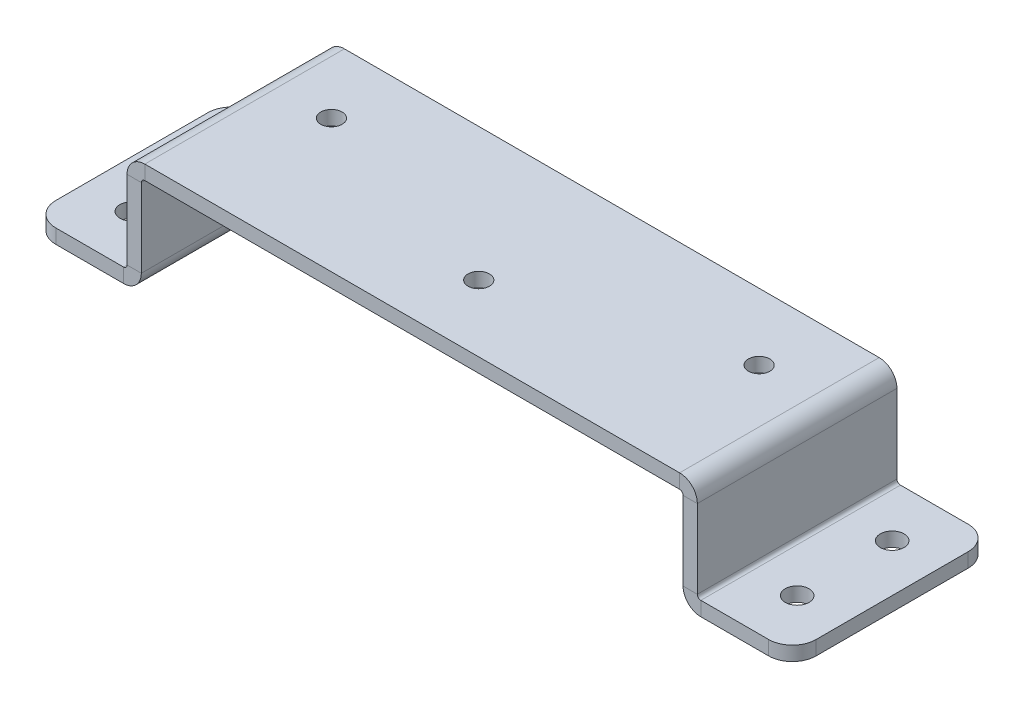
SolidWorks part; units mm, degrees
note: The reader was unsure of these and kept them because the rebuilt part matched: flange length of "모서리 플랜지1", "모서리 플랜지2".
ref_plane "정면" through (0, 0, 0) normal (0, 0, 1) x (1, 0, 0)
ref_plane "윗면" through (0, 0, 0) normal (0, 1, 0) x (1, 0, 0)
ref_plane "우측면" through (0, 0, 0) normal (1, 0, 0) x (0, 0, -1)
sketch "스케치1" plane through (0, 0, 0) normal (0, 1, 0) x (1, 0, 0)
  line L1 (60, -21) -> (-60, -21)
  line L2 (60, -21) -> (60, 21)
  line L3 (60, 21) -> (-60, 21)
  line L4 (-60, -21) -> (-60, 21)
  line L5 (60, -21) -> (-60, 21) construction
  line L6 (60, 21) -> (-60, -21) construction
  point P0 (0, 0)
  dimension "D1" = 120
  dimension "D2" = 42
base flange "베이스-플랜지1" sketch "스케치1" thickness 3 reverse thickness direction no parameters "D1"=0.7366
edge flange "모서리 플랜지1" sketch "스케치10" flange profiles "스케치10", "스케치11" flange angle 90 flange length 24 flange position material inside bend radius 0.7366 thickness 3 relief rectangular parameters "D6"=10, "D8"=1
sketch "스케치10" plane through (-60, -3, 0) normal (-1, 0, 0) x (0, 0, -1)
  line L0 (21, 0) -> (-21, 0) construction
  line L1 (21, 0) -> (-21, 0)
  line L2 (-21, 0) -> (-21, 21)
  line L3 (-21, 21) -> (21, 21)
  line L4 (21, 21) -> (21, 0)
sketch "스케치11" plane through (60, -3, 0) normal (1, 0, 0) x (0, 0, 1)
  line L0 (21, 0) -> (-21, 0) construction
  line L1 (21, 0) -> (-21, 0)
  line L2 (-21, 0) -> (-21, 21)
  line L3 (-21, 21) -> (21, 21)
  line L4 (21, 21) -> (21, 0)
bend "모서리 굽힘1" bend radius 0.7366 bend angle 90 parameters "D5"=1
bend "모서리 굽힘2" bend radius 0.7366 bend angle 90 parameters "D5"=2
edge flange "모서리 플랜지2" sketch "스케치16" flange profiles "스케치16", "스케치17" flange angle 90 flange length 20 flange position material inside bend radius 0.7366 thickness 3 relief rectangular parameters "D6"=10, "D8"=1
sketch "스케치16" plane through (-60, -24, 0) normal (0, -1, 0) x (0, 0, 1)
  line L2 (-21, 0) -> (-21, 20)
  line L3 (-21, 20) -> (21, 20)
  line L4 (21, 20) -> (21, 0)
  line L7 (-21, 0) -> (21, 0) construction
  line L8 (-21, 0) -> (21, 0)
sketch "스케치17" plane through (60, -24, 0) normal (0, -1, 0) x (0, 0, -1)
  line L0 (-21, 0) -> (21, 0) construction
  line L1 (-21, 0) -> (21, 0)
  line L2 (-21, 0) -> (-21, 20)
  line L3 (-21, 20) -> (21, 20)
  line L4 (21, 20) -> (21, 0)
bend "모서리 굽힘3" bend radius 0.7366 bend angle 90 parameters "D5"=3
bend "모서리 굽힘4" bend radius 0.7366 bend angle 90 parameters "D5"=4
fillet "필렛1" radius 5 4 edges at (-80, -22.5, 21) (-80, -22.5, -21) (80, -22.5, -21) (80, -22.5, 21)
sketch "스케치18" plane through (0, -24, 0) normal (0, -1, 0) x (1, 0, 0)
  line L0 (-70, -10) -> (-70, 10) construction
  line L1 (70, 10) -> (70, -10) construction
  line L2 (80, -16) -> (80, 16) construction
  line L3 (-80, 16) -> (-80, -16) construction
  point P0 (70, -10)
  point P1 (70, 10)
  point P2 (-70, 10)
  point P3 (-70, -10)
  point P11 (70, 0)
  dimension "D1" = 20
  dimension "D2" = 10
  dimension "D3" = 10
hole_wizard "M6 탭을 위한 탭 드릴1" positions "스케치19" profile "스케치20" hole size "M6" standard "ISO" end condition up to next
sketch "스케치19" plane through (0, -24, 0) normal (0, -1, 0) x (-1, 0, 0)
  point P0 (-70, 10)
  point P3 (-70, -10)
  point P6 (70, 10)
  point P9 (70, -10)
sketch "스케치20" plane through (70, -24, -10) normal (1, 0, 0) x (0, 0, -1)
  line L0 (0, 0) -> (0, 3)
  line L1 (0, 3) -> (2.5, 3)
  line L2 (2.5, 3) -> (2.5, 0)
  line L5 (2.5, 0) -> (0, 0)
  line L11 (0, -6.35) -> (0, 107.95) construction
  dimension "관통 구멍 지름" = 5
  dimension "관통 구멍 깊이" = 3
sketch "스케치21" plane through (0, 0, 0) normal (0, 1, 0) x (1, 0, 0)
  line L0 (-45, 7) -> (45, 7) construction
  point P0 (-45, 7)
  point P1 (0, -7)
  point P2 (45, 7)
  point P7 (0, 7)
  dimension "D1" = 14
  dimension "D2" = 7
  dimension "D3" = 90
hole_wizard "M4 여유 구멍1" positions "스케치22" profile "스케치23" hole size "M4" standard "ISO" end condition up to next
sketch "스케치22" plane through (0, 0, 0) normal (0, 1, 0) x (1, 0, 0)
  point P0 (-45, 7)
  point P3 (0, -7)
  point P6 (45, 7)
sketch "스케치23" plane through (-45, 0, -7) normal (1, 0, 0) x (0, 0, 1)
  line L0 (0, 0) -> (0, 3)
  line L1 (0, 3) -> (2.25, 3)
  line L2 (2.25, 3) -> (2.25, 0)
  line L5 (2.25, 0) -> (0, 0)
  line L11 (0, -6.35) -> (0, 107.95) construction
  dimension "관통 구멍 지름" = 4.5
  dimension "관통 구멍 깊이" = 3
sketch "굽힘 선1" [suppressed] plane through (0, 0, 0) normal (0, 1, 0) x (1, 0, 0)
sketch "경계 상자1" [suppressed] plane through (0, 0, 0) normal (0, 1, 0) x (1, 0, 0)
sheet metal parameters "판금2" thickness 3 parameters "D1"=0.7366
flat pattern "전개도2" [suppressed]
sketch "굽힘 선2" plane through (0, 0, 0) normal (0, 1, 0) x (1, 0, 0)
sketch3d "경계 상자2" [suppressed]
  line L0 (-75, -15, 0) -> (75, -15, 0) construction
  line L1 (-75, 15, 0) -> (75, 15, 0) construction
  line L2 (-75, -15, 0) -> (-75, 15, 0) construction
  line L3 (75, -15, 0) -> (75, 15, 0) construction
sheet metal parameters "판금3" thickness 3 parameters "D1"=0.7366
flat pattern "전개도2"
sketch "굽힘 선2" plane through (0, 0, 0) normal (0, 1, 0) x (1, 0, 0)
  line L0 (73.02, -15) -> (73.02, 15) construction
  line L1 (-73.02, 15) -> (-73.02, -15) construction
  line L2 (73.02, -15) -> (73.02, 15) construction
  line L3 (-73.02, 15) -> (-73.02, -15) construction
sketch3d "경계 상자2" [suppressed]
  line L0 (98.04, -15, 0) -> (-98.04, -15, 0) construction
  line L1 (98.04, 15, 0) -> (-98.04, 15, 0) construction
  line L2 (98.04, -15, 0) -> (98.04, 15, 0) construction
  line L3 (-98.04, -15, 0) -> (-98.04, 15, 0) construction
bend of the flat pattern "전개도-<모서리 굽힘1>1"
bend of the flat pattern "전개도-<모서리 굽힘2>1"
sheet metal parameters "판금4" thickness 3 parameters "D1"=0.7366
flat pattern "전개도2"
sketch "굽힘 선2" plane through (0, 0, 0) normal (0, 1, 0) x (1, 0, 0)
  line L0 (73.02, -15) -> (73.02, 15) construction
  line L1 (-73.02, 15) -> (-73.02, -15) construction
  line L2 (73.02, -15) -> (73.02, 15) construction
  line L3 (-73.02, 15) -> (-73.02, -15) construction
  line L4 (96.0601, -15) -> (96.0601, 15) construction
  line L5 (-96.0601, 15) -> (-96.0601, -15) construction
  line L6 (96.0601, -15) -> (96.0601, 15) construction
  line L7 (-96.0601, 15) -> (-96.0601, -15) construction
sketch3d "경계 상자2" [suppressed]
  line L0 (-117.0801, -15, 0) -> (117.0801, -15, 0) construction
  line L1 (-117.0801, 15, 0) -> (117.0801, 15, 0) construction
  line L2 (-117.0801, -15, 0) -> (-117.0801, 15, 0) construction
  line L3 (117.0801, -15, 0) -> (117.0801, 15, 0) construction
bend of the flat pattern "전개도-<모서리 굽힘1>1"
bend of the flat pattern "전개도-<모서리 굽힘2>1"
bend of the flat pattern "전개도-<모서리 굽힘3>1"
bend of the flat pattern "전개도-<모서리 굽힘4>1"
sheet metal parameters "판금5" thickness 3 parameters "D1"=0.7366
flat pattern "전개도2" [suppressed]
sketch "굽힘 선2" plane through (0, 0, 0) normal (0, 1, 0) x (1, 0, 0)
  line L0 (68.02, -21) -> (68.02, 21) construction
  line L1 (-68.02, 21) -> (-68.02, -21) construction
  line L2 (68.02, -21) -> (68.02, 21) construction
  line L3 (-68.02, 21) -> (-68.02, -21) construction
  line L4 (88.0601, -21) -> (88.0601, 21) construction
  line L5 (-88.0601, 21) -> (-88.0601, -21) construction
  line L6 (88.0601, -21) -> (88.0601, 21) construction
  line L7 (-88.0601, 21) -> (-88.0601, -21) construction
sketch3d "경계 상자2" [suppressed]
  line L0 (-109.0801, -21, 0) -> (109.0801, -21, 0) construction
  line L1 (-109.0801, 21, 0) -> (109.0801, 21, 0) construction
  line L2 (-109.0801, -21, 0) -> (-109.0801, 21, 0) construction
  line L3 (109.0801, -21, 0) -> (109.0801, 21, 0) construction
bend of the flat pattern "전개도-<모서리 굽힘1>1"
bend of the flat pattern "전개도-<모서리 굽힘2>1"
bend of the flat pattern "전개도-<모서리 굽힘3>1"
bend of the flat pattern "전개도-<모서리 굽힘4>1"
sketch "스케치18-1" plane through (-19.0801, -3, 0) normal (0, -1, 0) x (1, 0, 0)
  line L0 (-80, -10) -> (-80, 10) construction
  line L1 (80, 10) -> (80, -10) construction
  line L2 (128.1602, -16) -> (128.1602, 16)
  line L3 (-90, 16) -> (-90, -16)
  point P0 (80, -10)
  point P1 (80, 10)
  point P2 (-80, 10)
  point P3 (-80, -10)
  dimension "D1" = 20
  dimension "D2" = 48.1602
  dimension "D3" = 10
sheet metal parameters "판금6" thickness 3 parameters "D1"=0.7366
flat pattern "전개도2" [suppressed]
sketch "굽힘 선2" plane through (0, 0, 0) normal (0, 1, 0) x (1, 0, 0)
  line L0 (58.02, -21) -> (58.02, 21) construction
  line L1 (-58.02, 21) -> (-58.02, -21) construction
  line L2 (58.02, -21) -> (58.02, 21) construction
  line L3 (-58.02, 21) -> (-58.02, -21) construction
  line L4 (78.0601, -21) -> (78.0601, 21) construction
  line L5 (-78.0601, 21) -> (-78.0601, -21) construction
  line L6 (78.0601, -21) -> (78.0601, 21) construction
  line L7 (-78.0601, 21) -> (-78.0601, -21) construction
sketch3d "경계 상자2" [suppressed]
  line L0 (-99.0801, -21, 0) -> (99.0801, -21, 0) construction
  line L1 (-99.0801, 21, 0) -> (99.0801, 21, 0) construction
  line L2 (-99.0801, -21, 0) -> (-99.0801, 21, 0) construction
  line L3 (99.0801, -21, 0) -> (99.0801, 21, 0) construction
bend of the flat pattern "전개도-<모서리 굽힘1>1"
bend of the flat pattern "전개도-<모서리 굽힘2>1"
bend of the flat pattern "전개도-<모서리 굽힘3>1"
bend of the flat pattern "전개도-<모서리 굽힘4>1"
sketch "스케치18-1" plane through (-19.0801, -3, 0) normal (0, -1, 0) x (1, 0, 0)
  line L0 (-70, -10) -> (-70, 10) construction
  line L1 (70, 10) -> (70, -10) construction
  line L2 (118.1602, -16) -> (118.1602, 16)
  line L3 (-80, 16) -> (-80, -16)
  point P0 (70, -10)
  point P1 (70, 10)
  point P2 (-70, 10)
  point P3 (-70, -10)
  dimension "D1" = 20
  dimension "D2" = 48.1602
  dimension "D3" = 10
equation "\"e\"=10"
